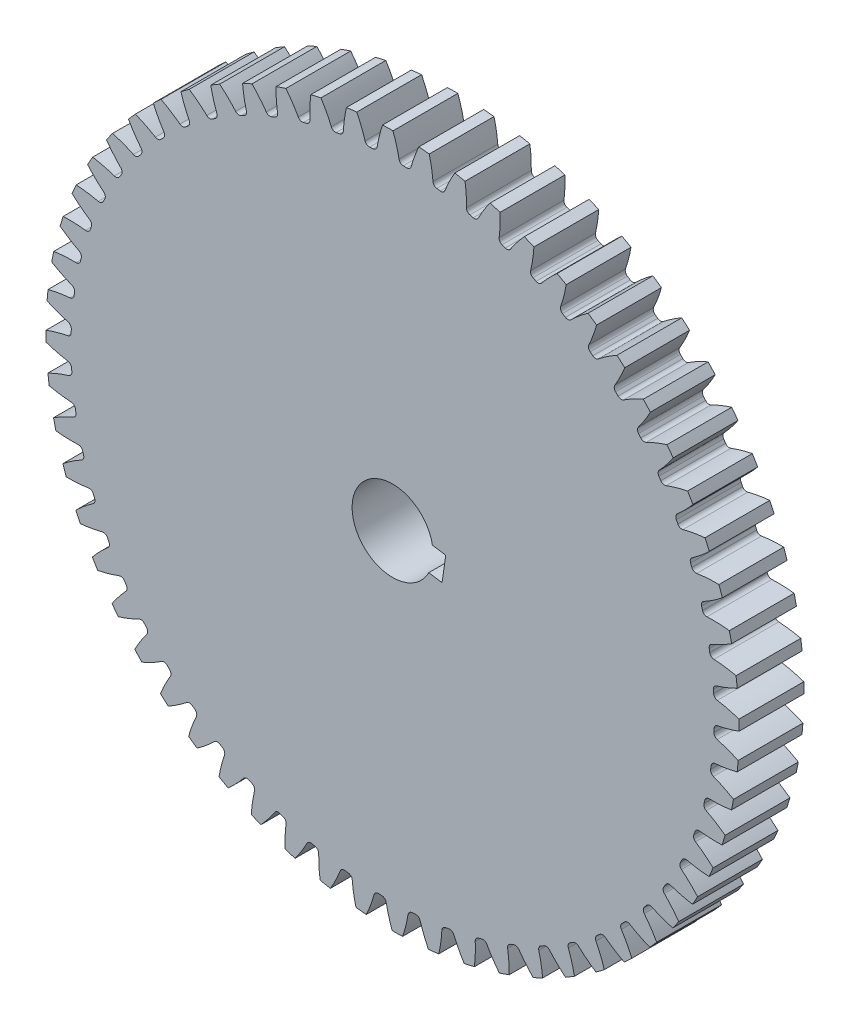
SolidWorks part; units mm, degrees
ref_plane "Front" through (0, 0, 0) normal (0, 0, 1) x (1, 0, 0)
ref_plane "Top" through (0, 0, 0) normal (0, 1, 0) x (1, 0, 0)
ref_plane "Right" through (0, 0, 0) normal (1, 0, 0) x (0, 0, -1)
sketch "Sketch3" plane through (0, 0, 0) normal (0, 0, 1) x (1, 0, 0)
  circle A0 centre (0, 0) radius 53.4737
  dimension "od" = 106.9474
extrude "gearBody" add sketch "Sketch3" along normal blind 10
sketch "Sketch2" plane through (0, 0, 0) normal (0, 0, 1) x (1, 0, 0)
  line L0 (0, 0) -> (46.2867, 19.1726) construction
  line L1 (62.4781, -12.4442) -> (0, 0) construction
  line L2 (0, 0) -> (36.3143, 0) construction
  line L3 (51.745, -0.6221) -> (51.6396, -3.3591) construction
  line L5 (51.6923, -1.9906) -> (0, 0) construction
  line L7 (0, 0) -> (50.1004, 0) construction
  arc A0 (50.0903, -1.0055) -> (50.0193, -2.8496) centre (0, 0) ccw construction
  arc A1 (53.4736, -0.062) -> (53.3201, -4.0505) centre (0, 0) ccw construction
  arc A2 (51.745, -0.6221) -> (51.6396, -3.3591) centre (0, 0) ccw construction
  arc A3 (49.5802, -2.1769) -> (49.6008, -1.6424) centre (0, 0) ccw
  arc A4 (62.4781, -12.4442) -> (50.0836, -2.8671) centre (44.6752, -22.6754) ccw
  arc A5 (62.4781, -12.4442) -> (63.2501, 7.6026) centre (0, 0) ccw
  arc A6 (63.2501, 7.6026) -> (50.1557, -0.993) centre (46.2867, 19.1726) cw
  arc A7 (49.6008, -1.6424) -> (50.1557, -0.993) centre (50.2847, -1.665) cw
  arc A8 (50.0836, -2.8671) -> (49.5802, -2.1769) centre (50.2638, -2.207) cw
  point P6 (63.2501, 7.6026)
  point P22 (62.4781, -12.4442)
  dimension "baseDia" = 100.2008
  dimension "od" = 106.9474
  dimension "pd" = 103.4975
  dimension "rd" = 99.256
  dimension "rFillet" = 0.6843
  dimension "pointX" = 63.2501
  dimension "pointY" = 7.6026
  dimension "CTT" = 2.737
  dimension "flankCenterAngle" = 22.5
extrude "toothCut" cut sketch "Sketch2" along normal through all
pattern_circular "CirPattern1" count 60 over 360 about axis through (0, 0, 10) along (0, 0, -1) of "toothCut"
ref_axis "toothSpace" through (0, 0, 0) along (0.9993, -0.0385, 0)
ref_axis "Axis2" through (53.2532, -4.8514, 0) along (-0.9959, 0.0907, 0)
sketch "hub1Dia" plane through (0, 0, 0) normal (0, 0, -1) x (-1, 0, 0)
  circle A0 centre (0, 0) radius 12.5
  dimension "hub1Dia" = 25
extrude "hub1" add sketch "hub1Dia" along normal blind 10
sketch "hub2Dia" plane through (0, 0, 10) normal (0, 0, 1) x (1, 0, 0)
  circle A0 centre (0, 0) radius 0.5
  dimension "hub2dia" = 1
sketch "boreDia" plane through (0, 0, 0) normal (0, 0, 1) x (1, 0, 0)
  circle A0 centre (0, 0) radius 6.25
  dimension "boreDia" = 12.5
extrude "bore" cut sketch "boreDia" against normal mid plane 25400
sketch "kwy1sketch" plane through (0, 0, 0) normal (0, 0, 1) x (1, 0, 0)
  line L0 (-5.3253, 0.7679) -> (0, 0) construction
  line L1 (8.2035, 0.8378) -> (7.6327, -3.1213)
  line L2 (7.6327, -3.1213) -> (2.6838, -2.4077)
  line L3 (8.2035, 0.8378) -> (3.2547, 1.5514)
  line L4 (2.6838, -2.4077) -> (0, 0)
  line L5 (0, 0) -> (3.2547, 1.5514)
  line L6 (0, 0) -> (49.5912, -1.9097) construction
  line L7 (7.9181, -1.1418) -> (0, 0) construction
  arc A7 (49.5802, -2.1769) -> (49.6008, -1.6424) centre (0, 0) ccw construction
  point P9 (7.9181, -1.1418)
  point P13 (-0.8883, 0.1281)
  dimension "kwy1width" = 4
  dimension "kwy1depth" = 8
  dimension "kwy1angle" = 6
  dimension "kwy1Depth2" = 5
extrude "kwy1" cut sketch "kwy1sketch" against normal mid plane 12700
sketch "kwy2sketch" plane through (0, 0, 0) normal (0, 0, 1) x (1, 0, 0)
  line L0 (49.5912, -1.9097) -> (0, 0) construction
  line L1 (0, 0) -> (-2.9774, -2.2269) construction
  line L2 (5.2084, 6.3932) -> (7.6042, 3.19)
  line L3 (7.6042, 3.19) -> (3.6003, 0.1953)
  line L4 (5.2084, 6.3932) -> (1.2045, 3.3984)
  line L5 (3.6003, 0.1953) -> (0, 0)
  line L6 (0, 0) -> (1.2045, 3.3984)
  arc A2 (49.5802, -2.1769) -> (49.6008, -1.6424) centre (0, 0) ccw construction
  point P10 (6.4063, 4.7916)
  dimension "kwy2angle" = 39
  dimension "kwy2Width" = 4
  dimension "kwy2depth" = 8
  dimension "kwy2Depth2" = 5
sketch "kwy3sketch" plane through (0, 0, 0) normal (0, 0, 1) x (1, 0, 0)
  line L0 (49.5912, -1.9097) -> (0, 0) construction
  line L1 (0, 0) -> (-0.3839, -2.6623) construction
  line L2 (-0.8378, 8.2035) -> (3.1213, 7.6327)
  line L3 (3.1213, 7.6327) -> (2.4077, 2.6838)
  line L4 (-0.8378, 8.2035) -> (-1.5514, 3.2547)
  line L5 (2.4077, 2.6838) -> (0, 0)
  line L6 (-1.5514, 3.2547) -> (0, 0)
  point P10 (1.1418, 7.9181)
  dimension "kwy3angle" = 84
  dimension "kwy3depth" = 8
  dimension "kwy3width" = 4
  dimension "kwy3Depth2" = 5
sketch "kwy4sketch" plane through (0, 0, 0) normal (0, 0, 1) x (1, 0, 0)
  line L0 (49.5912, -1.9097) -> (0, 0) construction
  line L1 (0, 0) -> (1.2597, -1.6842) construction
  line L2 (-3.19, 7.6042) -> (-6.3932, 5.2084)
  line L3 (-6.3932, 5.2084) -> (-3.3984, 1.2045)
  line L4 (-3.3984, 1.2045) -> (0, 0)
  line L5 (-0.1953, 3.6003) -> (0, 0)
  line L6 (-3.19, 7.6042) -> (-0.1953, 3.6003)
  point P15 (-4.7916, 6.4063)
  dimension "kwy4angle" = 129
  dimension "kwy4depth" = 8
  dimension "kwy4width" = 4
  dimension "kwy4Depth2" = 5
sketch "kwy5sketch" plane through (0, 0, 0) normal (0, 0, 1) x (1, 0, 0)
  line L0 (49.5912, -1.9097) -> (0, 0) construction
  line L1 (0, 0) -> (1.7878, -0.2578) construction
  line L2 (-7.6327, 3.1213) -> (-8.2035, -0.8378)
  line L3 (-8.2035, -0.8378) -> (-3.2547, -1.5514)
  line L4 (-7.6327, 3.1213) -> (-2.6838, 2.4077)
  line L5 (-3.2547, -1.5514) -> (0, 0)
  line L6 (-2.6838, 2.4077) -> (0, 0)
  point P10 (-7.9181, 1.1418)
  dimension "kwy5width" = 4
  dimension "kwy5depth" = 8
  dimension "kwy5angle" = 174
  dimension "kwy5Depth2" = 5
sketch "kwy6sketch" plane through (0, 0, 0) normal (0, 0, 1) x (1, 0, 0)
  line L0 (49.5912, -1.9097) -> (0, 0) construction
  line L1 (0, 0) -> (1.4453, 1.081) construction
  line L2 (-7.6042, -3.19) -> (-5.2084, -6.3932)
  line L3 (-5.2084, -6.3932) -> (-1.2045, -3.3984)
  line L4 (-7.6042, -3.19) -> (-3.6003, -0.1953)
  line L5 (-1.2045, -3.3984) -> (0, 0)
  line L6 (-3.6003, -0.1953) -> (0, 0)
  point P10 (-6.4063, -4.7916)
  dimension "kwy6angle" = 219
  dimension "kwy6width" = 4
  dimension "kwy6depth" = 8
  dimension "kwy6Depth2" = 5
sketch "kwy7sketch" plane through (0, 0, 0) normal (0, 0, 1) x (1, 0, 0)
  line L0 (49.5912, -1.9097) -> (0, 0) construction
  line L1 (0, 0) -> (0.2886, 2.0013) construction
  line L2 (-3.1213, -7.6327) -> (0.8378, -8.2035)
  line L3 (-3.1213, -7.6327) -> (-2.4077, -2.6838)
  line L4 (0.8378, -8.2035) -> (1.5514, -3.2547)
  line L5 (-2.4077, -2.6838) -> (0, 0)
  line L6 (1.5514, -3.2547) -> (0, 0)
  point P10 (-1.1418, -7.9181)
  dimension "kwy7angle" = 84
  dimension "kwy7width" = 4
  dimension "kwy7depth" = 8
  dimension "kwy7angle1" = 264
  dimension "kwy7Depth2" = 5
sketch "kwy8sketch" plane through (0, 0, 0) normal (0, 0, 1) x (1, 0, 0)
  line L0 (49.5912, -1.9097) -> (0, 0) construction
  line L1 (0, 0) -> (-1.076, 1.4386) construction
  line L2 (3.19, -7.6042) -> (6.3932, -5.2084)
  line L3 (6.3932, -5.2084) -> (3.3984, -1.2045)
  line L4 (3.19, -7.6042) -> (0.1953, -3.6003)
  line L5 (3.3984, -1.2045) -> (0, 0)
  line L6 (0.1953, -3.6003) -> (0, 0)
  point P10 (4.7916, -6.4063)
  dimension "kwy8angle" = 309
  dimension "kwy8width" = 4
  dimension "kwy8depth" = 8
  dimension "kwy8Depth2" = 5
sketch "centerLine" plane through (0, 0, 0) normal (0, 1, 0) x (1, 0, 0)
  line L0 (0, 36.4807) -> (0, -59.6309) construction
ref_plane "CB1plane" through (0, 0, -10) normal (0, 0, -1) x (-1, 0, 0)
sketch "CB1diameter" plane through (0, 0, -10) normal (0, 0, -1) x (-1, 0, 0)
  circle A0 centre (0, 0) radius 0.5
  dimension "CB1diameter" = 1
ref_plane "CB2plane" through (0, 0, 10) normal (0, 0, 1) x (1, 0, 0)
sketch "CB2diameter" plane through (0, 0, 10) normal (0, 0, 1) x (1, 0, 0)
  circle A0 centre (0, 0) radius 0.5
  dimension "CB2diameter" = 1
ref_axis "Axis1" through (0, 0, 50) along (0, 0, -1)
hole_wizard "ss1Hub1" positions "ss1TriangleH1" profile "ss1SketchH1" hole size "Ø3.0" standard "ANSI Metric"
sketch3d "ss1TriangleH1"
  line L0 (0, 0, 0) -> (12.372, -1.784, -5) construction
  line L1 (12.372, -1.784, -5) -> (12.372, -1.784, 0) construction
  line L2 (12.372, -1.784, 0) -> (0, 0, 0) construction
  line L7 (12.372, -1.784, 0) -> (0, 0, 0) construction
  line L21 (2.8399, -0.1094, 0) -> (0, 0, 0) construction
  line L22 (0, 0, 0) -> (49.5912, -1.9097, 0) construction
  circle A0 centre (0, 0, 0) radius 12.5 construction
  point P1 (12.372, -1.784, -5)
  point P10 (0, 0, -12.5)
  dimension "ss1HeightH1" = 5
  dimension "ss1AngleH1" = 6
sketch "ss1SketchH1" plane through (12.372, -1.784, -5) normal (0, 0, 1) x (0.1427, 0.9898, 0)
  line L0 (0, 0) -> (0, 13.4013)
  line L1 (0, 13.4013) -> (1.5, 12.5)
  line L2 (1.5, 12.5) -> (1.5, 0)
  line L5 (1.5, 0) -> (0, 0)
  line L10 (0, 13.4013) -> (-1.5, 12.5) construction
  line L11 (0, -6.35) -> (0, 107.95) construction
  dimension "Hole Dia." = 3
  dimension "Hole Depth" = 12.5
  dimension "Drill Angle" = 118
hole_wizard "ss3Hub1" positions "ss3TriangleH1" profile "ss3SketchH1" hole size "Ø3.0" standard "ANSI Metric"
sketch3d "ss3TriangleH1"
  line L0 (0, 0, 0) -> (1.784, 12.372, -5) construction
  line L1 (1.784, 12.372, -5) -> (1.784, 12.372, 0) construction
  line L2 (1.784, 12.372, 0) -> (0, 0, 0) construction
  line L6 (49.5912, -1.9097, 0) -> (0, 0, 0) construction
  line L9 (0, 0, 0) -> (49.5912, -1.9097, 0) construction
  circle A0 centre (0, 0, 0) radius 12.5 construction
  arc A2 (49.6008, -1.6424, 0) -> (49.5802, -2.1769, 0) centre (0, 0, 0) ccw construction
  point P0 (1.784, 12.372, -5)
  point P8 (0, 0, -12.5)
  point P27 (0, 0, -49.628)
  dimension "ss3HeightH1" = 5
  dimension "ss3AngleH1" = 84
sketch "ss3SketchH1" plane through (1.784, 12.372, -5) normal (0, 0, 1) x (-0.9898, 0.1427, 0)
  line L0 (0, 0) -> (0, 13.4013)
  line L1 (0, 13.4013) -> (1.5, 12.5)
  line L2 (1.5, 12.5) -> (1.5, 0)
  line L5 (1.5, 0) -> (0, 0)
  line L10 (0, 13.4013) -> (-1.5, 12.5) construction
  line L11 (0, -6.35) -> (0, 107.95) construction
  dimension "Hole Dia." = 3
  dimension "Hole Depth" = 12.5
  dimension "Drill Angle" = 118
sketch3d "3DSketch1" plane through (0, 0, 0) normal (0, 0, 1) x (1, 0, 0)
ref_plane "Plane1" through (1.1132, 7.7202, 0) normal (-0.1427, -0.9898, 0) x (0.9898, -0.1427, 0)
sketch "Sketch6" plane through (1.1132, 7.7202, 0) normal (-0.1427, -0.9898, 0) x (0.9898, -0.1427, 0)
  line L0 (-12.5, -10) -> (12.5, -10) construction
  line L1 (-3, 0) -> (3, 0)
  line L2 (-3, 0) -> (-3, -10)
  line L3 (-3, -10) -> (3, -10)
  line L4 (3, 0) -> (3, -10)
  line L5 (-3, 0) -> (3, -10) construction
  line L6 (-3, -10) -> (3, 0) construction
  point P0 (0, -5)
  dimension "D1" = 6
extrude "Cut-Extrude1" cut sketch "Sketch6" against normal blind 2.5
